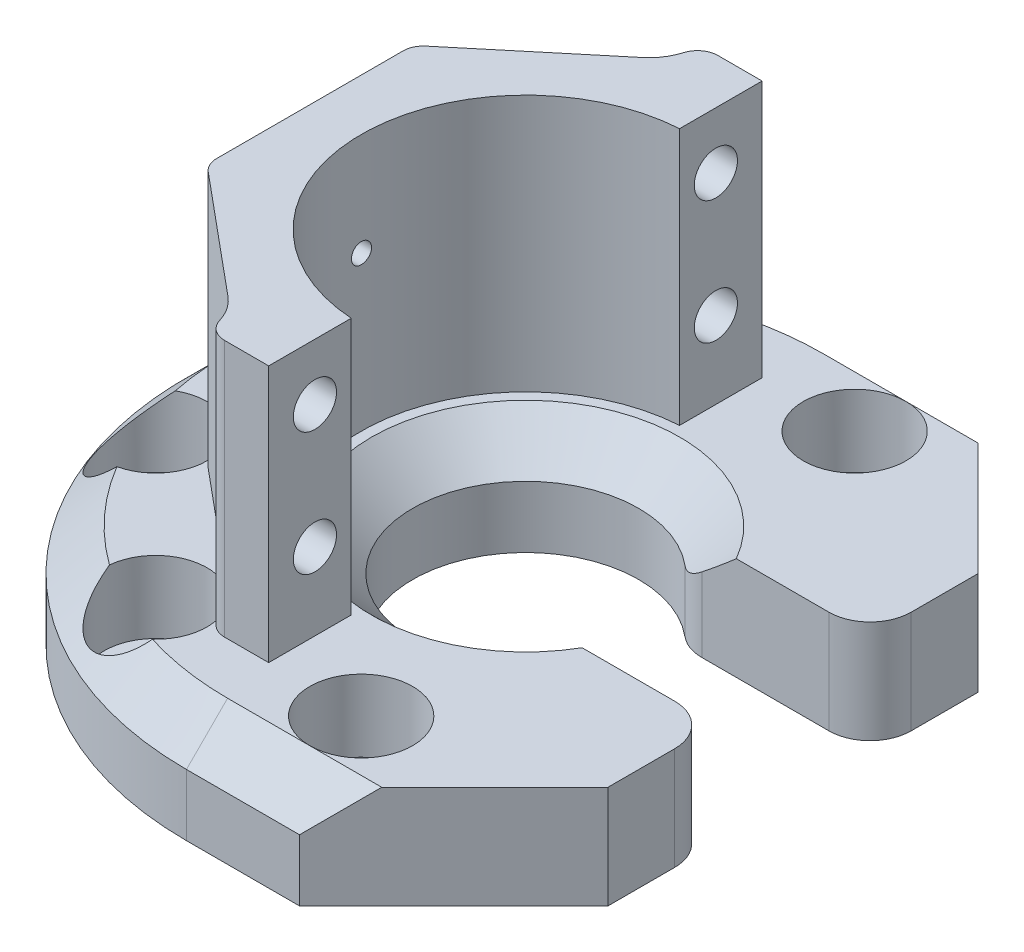
SolidWorks part; units mm, degrees
material "7075-T6 (SN)"
ref_plane "Front" through (0, 0, 0) normal (0, 0, 1) x (1, 0, 0)
ref_plane "Top" through (0, 0, 0) normal (0, 1, 0) x (1, 0, 0)
ref_plane "Right" through (0, 0, 0) normal (1, 0, 0) x (0, 0, -1)
sketch "Sketch1" plane through (0, 0, 0) normal (0, 1, 0) x (1, 0, 0)
  circle A0 centre (0, 0) radius 33
  dimension "D1" = 66
extrude "Boss-Extrude1" add sketch "Sketch1" along normal mid plane 10
sketch "Sketch2" plane through (0, 5, 0) normal (0, 1, 0) x (1, 0, 0)
  circle A0 centre (0, 0) radius 11
  dimension "D1" = 22
extrude "Cut-Extrude1" cut sketch "Sketch2" against normal through all
sketch "Sketch12" plane through (0, 5, 0) normal (0, 1, 0) x (1, 0, 0)
  line L0 (0, -33) -> (33, -33)
  line L1 (33, 33) -> (33, -33)
  line L2 (0, 33) -> (0, 16)
  line L3 (0, 33) -> (33, 33)
  line L4 (0, -33) -> (0, -16)
  line L6 (0, 0) -> (33, 0) construction
  circle A0 centre (0, 0) radius 33 construction
  arc A1 (0, 16) -> (0, -16) centre (0, 0) cw
  circle A4 centre (0, 0) radius 33 construction
  circle A5 centre (0, 0) radius 11 construction
  dimension "D1" = 16
extrude "Boss-Extrude4" add sketch "Sketch12" against normal through all
chamfer "Chamfer1" distance 4 angle 45 4 edges at (16.5, 5, -33) (16.5, 5, 33) (-33, 5, 0) (0, 5, 11)
hole_wizard "CBORE for M5 SHCS1" positions "Sketch37" profile "Sketch38" counterbore size "M5" standard "ANSI Metric" end condition up to next
sketch "Sketch37" plane through (0, 5, 0) normal (0, 1, 0) x (1, 0, 0)
  line L0 (0, 0) -> (0, 24) construction
  line L3 (-12, 24) -> (8, 24) construction
  line L4 (0, 0) -> (-26, 0) construction
  line L5 (-26, 0) -> (-26, 10) construction
  point P0 (-12, 24)
  point P14 (8, 24)
  point P21 (-26, 10)
  dimension "D1" = 24
  dimension "D2" = 12
  dimension "D3" = 20
  dimension "D4" = 26
  dimension "D5" = 10
sketch "Sketch38" plane through (-12, 5, -24) normal (1, 0, 0) x (0, 0, 1)
  line L0 (0, 0) -> (0, 10.001)
  line L1 (0, 10.001) -> (2.65, 10.001)
  line L3 (2.65, 10.001) -> (2.65, 7)
  line L4 (2.65, 7) -> (5, 7)
  line L5 (5, 7) -> (5, 0)
  line L7 (5, 0) -> (0, 0)
  line L11 (0, -6.35) -> (0, 107.95) construction
  dimension "Thru Hole Dia." = 5.3
  dimension "Thru Hole Depth" = 10.001
  dimension "C'Bore Dia." = 10
  dimension "C'Bore Depth" = 7
mirror "Mirror2" about plane through (0, 0, 0) normal (0, 0, 1) of "CBORE for M5 SHCS1"
sketch "Sketch40" plane through (0, 5, 0) normal (0, 1, 0) x (1, 0, 0)
  line L0 (11, 33) -> (26, 18)
  line L3 (33, -33) -> (0, -33) construction
  line L4 (26, -18) -> (11, -33)
  line L6 (11, -33) -> (33, -33)
  line L7 (33, -33) -> (33, 33)
  line L8 (33, 33) -> (11, 33)
  line L9 (26, 18) -> (26, -18)
  circle A1 centre (0, 0) radius 11 construction
  dimension "D1" = 26
  dimension "D2" = 45
  dimension "D3" = 15
extrude "Cut-Extrude12" cut sketch "Sketch40" against normal through all
sketch "Sketch43" plane through (0, 5, 0) normal (0, 1, 0) x (1, 0, 0)
  line L0 (26, 18) -> (26, -18) construction
  line L1 (43.9533, 7.5) -> (8.0467, 7.5)
  line L2 (43.9533, 7.5) -> (43.9533, -7.5)
  line L3 (43.9533, -7.5) -> (8.0467, -7.5)
  line L4 (8.0467, 7.5) -> (8.0467, -7.5)
  line L5 (43.9533, 7.5) -> (8.0467, -7.5) construction
  line L6 (43.9533, -7.5) -> (8.0467, 7.5) construction
  circle A0 centre (0, 0) radius 11 construction
  point P0 (26, 0)
  dimension "D1" = 15
extrude "Cut-Extrude13" cut sketch "Sketch43" against normal through all
fillet "Fillet1" radius 4 4 edges at (26, 0, 7.5) (26, 0, -7.5) (8.0467, -2, 7.5) (8.0467, -2, -7.5)
sketch "Sketch44" plane through (0, 5, 0) normal (0, 1, 0) x (1, 0, 0)
  line L0 (-21, 10) -> (-21, -10)
  line L1 (-8.8007, 20.1576) -> (-21, 10)
  line L2 (-21, -10) -> (-8.8007, -20.1576)
  line L10 (-1, 28.9828) -> (-1, 15.9687)
  line L11 (-1, -15.9687) -> (-1, -28.9828)
  circle A1 centre (-26, 10) radius 5 construction
  arc A2 (-28.4464, 5.6394) -> (-24.8938, 14.8761) centre (-26, 10) ccw construction
  arc A3 (-24.8938, -14.8761) -> (-28.4464, -5.6394) centre (-26, -10) ccw construction
  arc A25 (0, 29) -> (-8.6239, 27.6881) centre (0, 0) ccw construction
  arc A27 (-8.6239, -27.6881) -> (0, -29) centre (0, 0) ccw construction
  arc A28 (-1, 28.9828) -> (-8.6239, 27.6881) centre (0, 0) ccw
  arc A29 (-8.6239, -27.6881) -> (-1, -28.9828) centre (0, 0) ccw
  arc A30 (-1, 15.9687) -> (-1, -15.9687) centre (0, 0) ccw
  circle A32 centre (-12, 24) radius 5
  arc A33 (-8.8007, 20.1576) -> (-8.6239, 27.6881) centre (-12, 24) ccw
  circle A34 centre (-12, -24) radius 5
  arc A35 (-8.6239, -27.6881) -> (-8.8007, -20.1576) centre (-12, -24) ccw
  dimension "D2" = 16
  dimension "D1" = 1
  dimension "D3" = 0
  dimension "D4" = 0
extrude "Boss-Extrude5" add sketch "Sketch44" along normal blind 25
sketch "Sketch45" plane through (-1, 0, 0) normal (1, 0, 0) x (0, 0, -1)
  line L0 (-18, 5) -> (-29, 5) construction
  line L1 (-28.9828, 30) -> (-24, 30)
  line L2 (-28.9828, 30) -> (-28.9828, 5)
  line L3 (-28.9828, 5) -> (-24, 5)
  line L4 (-24, 30) -> (-24, 5)
  line L5 (-24, 17.5) -> (24, 17.5) construction
  line L6 (29, 5) -> (24, 5)
  line L7 (29, 5) -> (29, 30)
  line L8 (29, 30) -> (24, 30)
  line L9 (24, 5) -> (24, 30)
  line L11 (0, 17.5) -> (0, 0) construction
  dimension "D1" = 48
extrude "Cut-Extrude14" cut sketch "Sketch45" against normal through all
fillet "Fillet2" radius 2 4 edges at (-7, 17.5, -24) (-7, 17.5, 24) (-21, 17.5, 10) (-21, 17.5, -10)
hole_wizard "M5x0.8 Tapped Hole1" positions "Sketch46" profile "Sketch47" tap size "M5x0.8" standard "ANSI Metric" end condition through all
sketch "Sketch46" plane through (-1, 0, 0) normal (1, 0, 0) x (0, 0, -1)
  line L1 (-19.5, 24.5) -> (19.5, 24.5)
  line L2 (-19.5, 24.5) -> (-19.5, 12.5)
  line L3 (-19.5, 12.5) -> (19.5, 12.5)
  line L4 (19.5, 24.5) -> (19.5, 12.5)
  line L5 (0, 12.5) -> (0, 0) construction
  line L7 (24, 30) -> (15.9687, 30) construction
  point P0 (-19.5, 24.5)
  point P2 (-19.5, 12.5)
  point P4 (19.5, 12.5)
  point P6 (19.5, 24.5)
  dimension "D1" = 39
  dimension "D2" = 12
  dimension "D3" = 5.5
sketch "Sketch47" plane through (-1, 24.5, 19.5) normal (0, 1, 0) x (0, 0, -1)
  line L0 (0, 0) -> (0, 32)
  line L1 (0, 32) -> (2.1, 32)
  line L2 (2.1, 32) -> (2.1, 0)
  line L5 (2.1, 0) -> (0, 0)
  line L11 (0, -6.35) -> (0, 107.95) construction
  dimension "Thru Tap Drill Dia." = 4.2
  dimension "Thru Tap Drill Depth" = 32
cosmetic thread "Hole Thread9" parameters "D1"=9, "D2"=5
cosmetic thread "Hole Thread10" parameters "D1"=9, "D2"=5
cosmetic thread "Hole Thread11" parameters "D1"=9, "D2"=5
cosmetic thread "Hole Thread12" parameters "D1"=9, "D2"=5
sketch "Sketch48" plane through (0, 0, 0) normal (-1, 0, 0) x (0, 0, 1)
  line L0 (-33, -5) -> (33, -5) construction
  line L1 (0, -5) -> (0, 20) construction
  circle A0 centre (0, 20) radius 0.975
  dimension "D1" = 1.95
  dimension "D2" = 25
extrude "Cut-Extrude15" cut sketch "Sketch48" along normal through all
